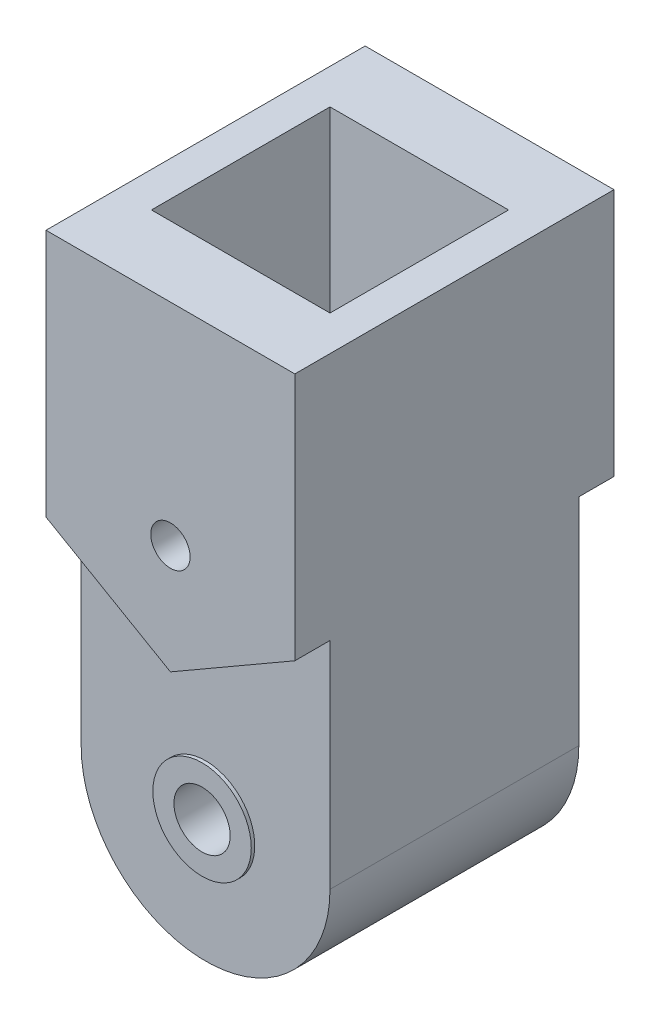
SolidWorks part; units mm, degrees
material "PETG"
ref_plane "Front Plane" through (0, 0, 0) normal (0, 0, 1) x (1, 0, 0)
ref_plane "Top Plane" through (0, 0, 0) normal (0, 1, 0) x (1, 0, 0)
ref_plane "Right Plane" through (0, 0, 0) normal (1, 0, 0) x (0, 0, -1)
sketch "Sketch1" plane through (0, 0, 0) normal (0, 1, 0) x (1, 0, 0)
  line L1 (-12.7, -12.7) -> (12.7, -12.7)
  line L2 (-12.7, -12.7) -> (-12.7, 12.7)
  line L3 (-12.7, 12.7) -> (12.7, 12.7)
  line L4 (12.7, -12.7) -> (12.7, 12.7)
  line L5 (-17.7, -17.7) -> (17.7, -17.7)
  line L6 (-17.7, -17.7) -> (-17.7, 17.7)
  line L7 (-17.7, 17.7) -> (17.7, 17.7)
  line L8 (17.7, -17.7) -> (17.7, 17.7)
  point P8 (0, -17.7)
  point P9 (0, -12.7)
  point P12 (-17.7, 0)
  point P13 (-12.7, 0)
  dimension "D1" = 25.4
  dimension "D2" = 5
extrude "Boss-Extrude1" add sketch "Sketch1" along normal blind 50
extrude "Boss-Extrude2" add sketch "Sketch1<3>" against normal blind 10 contours L1 L4 L3 L2 | L5 L8 L7 L6 L4 L1 L2 L3 region at (0, 0, 0) region at (-17.1994, 0, 0)
sketch "Sketch1<3>" plane through (0, 0, 0) normal (0, 1, 0) x (1, 0, 0) same geometry as "Sketch1"
sketch "Sketch2" plane through (0, 0, -17.7) normal (0, 0, 1) x (1, 0, 0)
  line L0 (-17.7, 50) -> (-17.7, -10) construction
  line L1 (17.7, 50) -> (17.7, -10) construction
  line L4 (-17.7, -10) -> (17.7, -10) construction
  line L5 (-17.7, -16) -> (-17.7, -10)
  line L6 (17.7, -10) -> (17.7, -16)
  line L7 (17.7, -10) -> (-17.7, -10)
  circle A0 centre (0, -16) radius 4
  arc A1 (-17.7, -16) -> (17.7, -16) centre (0, -16) ccw
  circle A2 centre (0, -16) radius 11 construction
  dimension "D1" = 8
  dimension "D2" = 6
  dimension "D3" = 22
extrude "Boss-Extrude5" add sketch "Sketch2" along normal up to surface (35.4 mm away) up to face at (0, 20, 17.7)
ref_plane "Plane1" through (0, -33.7, 0) normal (0, -1, 0) x (-1, 0, 0)
sketch "Sketch3" plane through (0, -33.7, 0) normal (0, -1, 0) x (-1, 0, 0)
  circle A0 centre (0, 0) radius 3.15
  dimension "D1" = 6.3
extrude "Cut-Extrude1" cut sketch "Sketch3" against normal through all
sketch "Sketch4" plane through (0, -33.7, 0) normal (0, -1, 0) x (-1, 0, 0)
  circle A0 centre (0, 0) radius 5.5
  dimension "D1" = 11
extrude "Cut-Extrude2" cut sketch "Sketch4" against normal offset from surface (25.7 mm away) 8 up to face at (0, 0, 3.15)
sketch "Sketch5" plane through (0, 0, 17.7) normal (0, 0, 1) x (1, 0, 0)
  circle A0 centre (0, -16) radius 7
  circle A1 centre (0, -16) radius 4 construction
  circle M6 centre (0, -16) radius 4
  dimension "D1" = 14
extrude "Boss-Extrude6" add sketch "Sketch5" along normal blind 0.5 contours A0 M6 region at (-6.802, -16, 17.7)
mirror "Mirror1" about plane through (0, 0, 0) normal (0, 0, 1) of "Boss-Extrude6"
sketch "Sketch6" plane through (0, 0, 17.7) normal (0, 0, 1) x (1, 0, 0)
  line L5 (8.85, -31.3286) -> (52.1513, -6.3286) construction
  line L6 (-8.85, -0.6714) -> (34.4513, 24.3286) construction
  line L7 (52.1513, -6.3286) -> (34.4513, 24.3286) construction
  line L8 (0, -16) -> (0, -79.4793) construction
  line L9 (17.7, 50) -> (17.7, -16) construction
  line L10 (17.7, 14.6573) -> (-17.7, 14.6573)
  line L11 (17.7, 14.6573) -> (17.7, 50)
  line L12 (17.7, 50) -> (-17.7, 50)
  line L13 (-17.7, 14.6573) -> (-17.7, 50)
  line L14 (17.7, 14.6573) -> (0, 4.4382)
  line L15 (0, 4.4382) -> (-17.7, 14.6573)
  arc A0 (-17.7, -16) -> (17.7, -16) centre (0, -16) ccw construction
  circle A1 centre (0, -16) radius 17.7
  line M4 (-17.7, 50) -> (-17.7, -16)
  line M6 (17.7, -16) -> (17.7, 50)
  line M7 (17.7, 50) -> (-17.7, 50)
  dimension "D1" = 50
  dimension "D2" = 120
extrude "Boss-Extrude7" add sketch "Sketch6" along normal blind 5 contours L14 L10 M4 | L10 M6 M7 M4 region at (0, 11.2509, 17.7) region at (0, 32.3286, 17.7)
sketch "Sketch7" plane through (0, 0, 22.7) normal (0, 0, 1) x (1, 0, 0)
  line L0 (17.7, 50) -> (-17.7, 50) construction
  line L1 (17.7, 20) -> (0, 20) construction
  line L2 (17.7, 14.6573) -> (17.7, 50) construction
  line L3 (0, 20) -> (-17.7, 20) construction
  line L4 (-17.7, 50) -> (-17.7, 14.6573) construction
  circle A0 centre (0, 20) radius 2.8
  dimension "D1" = 30
  dimension "D2" = 5.6
extrude "Cut-Extrude3" cut sketch "Sketch7" against normal up to next
mirror "Mirror2" about plane through (0, 0, 0) normal (0, 0, 1) of "Boss-Extrude7", "Cut-Extrude3"
